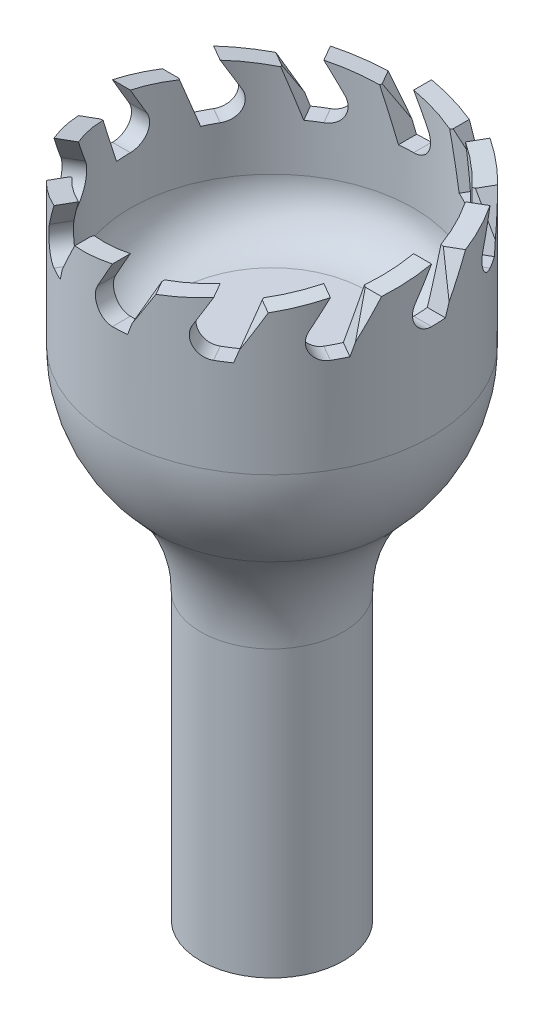
SolidWorks part; units mm, degrees
ref_plane "Front Plane" through (0, 0, 0) normal (0, 0, 1) x (1, 0, 0)
ref_plane "Top Plane" through (0, 0, 0) normal (0, 1, 0) x (1, 0, 0)
ref_plane "Right Plane" through (0, 0, 0) normal (1, 0, 0) x (0, 0, -1)
sketch "Sketch1" plane through (0, 0, 0) normal (0, 0, 1) x (1, 0, 0)
  line L0 (0, 0) -> (-4.7625, 0)
  line L1 (-4.7625, 0) -> (-4.7625, 19.05)
  line L2 (-10.668, 33.3071) -> (-10.668, 43.3071)
  line L3 (-10.668, 43.3071) -> (-9.468, 43.3071)
  line L4 (-9.468, 43.3071) -> (-9.468, 36.4821)
  line L5 (-6.293, 33.3071) -> (0, 33.3071)
  line L6 (0, 33.3071) -> (0, 0)
  arc A0 (-4.7625, 19.05) -> (-7.7153, 26.1786) centre (-14.8438, 19.05) ccw
  arc A1 (-7.7153, 26.1786) -> (-10.668, 33.3071) centre (-0.5867, 33.3071) cw
  arc A2 (-9.468, 36.4821) -> (-6.293, 33.3071) centre (-6.293, 36.4821) ccw
  point P8 (-9.0627, 32.8677)
  point P13 (0, 0)
  point P14 (-10.668, 29.8679)
  point P17 (-9.468, 33.3071)
  dimension "D1" = 4.7625
  dimension "D7" = 3.175
  dimension "D2" = 19.05
  dimension "D3" = 10.668
  dimension "D4" = 10
  dimension "D5" = 45
  dimension "D6" = 1.2
revolve "Revolve1" add sketch "Sketch1" angle 360 about L6
sketch "Sketch2" plane through (0, 0, 0) normal (0, 0, 1) x (1, 0, 0)
  line L0 (0, 43.3071) -> (1.0461, 41.4953)
  line L1 (0, 39.6834) -> (-0.9669, 39.6834)
  line L2 (9.468, 43.3071) -> (-9.468, 43.3071) construction
  line L3 (10.668, 43.3071) -> (-10.668, 43.3071) construction
  line L4 (2.9344, 42.6834) -> (4.6665, 39.6834)
  line L5 (4.6665, 39.6834) -> (4.6665, 43.7927)
  line L6 (4.6665, 43.7927) -> (-2.4408, 43.7927)
  line L8 (0, 43.3071) -> (2.9344, 42.6834)
  line L9 (-0.9669, 39.6834) -> (-2.4408, 43.7927)
  arc A0 (1.0461, 41.4953) -> (0, 39.6834) centre (0, 40.8913) cw
  point P4 (2.9672, 42.8646)
  dimension "D1" = 60
  dimension "D2" = 3
  dimension "D3" = 3
  dimension "D4" = 12
extrude "Cut-Extrude1" cut sketch "Sketch2" against normal blind 19.304
ref_axis "Axis1" through (0, 36.4821, 0) along (0, 1, 0)
pattern_circular "CirPattern2" count 12 over 360 about axis through (0, 36.4821, 0) along (0, 1, 0) of "Cut-Extrude1"
